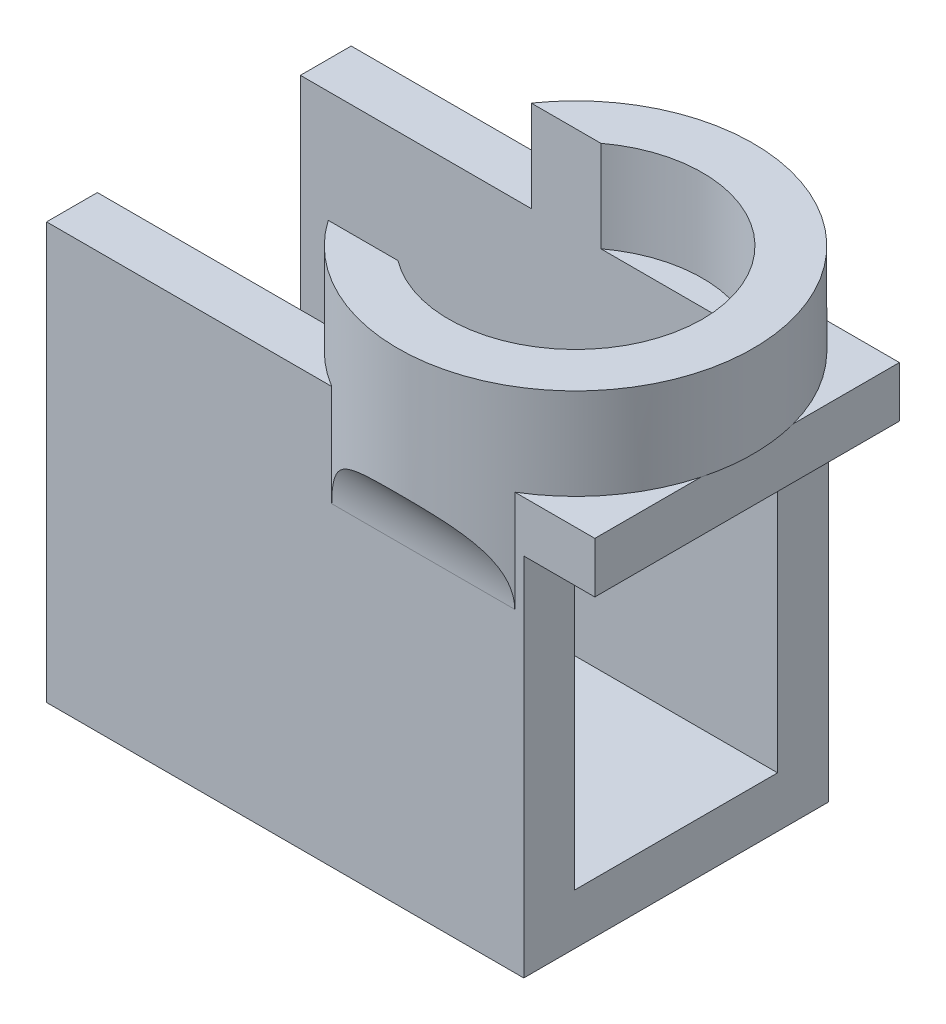
SolidWorks part; units mm, degrees
ref_plane "Front Plane" through (0, 0, 0) normal (0, 0, 1) x (1, 0, 0)
ref_plane "Top Plane" through (0, 0, 0) normal (0, 1, 0) x (1, 0, 0)
ref_plane "Right Plane" through (0, 0, 0) normal (1, 0, 0) x (0, 0, -1)
sketch "Sketch1" plane through (0, 0, 0) normal (0, 1, 0) x (1, 0, 0)
  line L1 (0, 0) -> (54, 0)
  line L2 (0, 0) -> (0, 30)
  line L3 (0, 30) -> (54, 30)
  line L4 (54, 0) -> (54, 30)
  dimension "D1" = 54
  dimension "D2" = 30
extrude "Boss-Extrude1" add sketch "Sketch1" along normal blind 5
sketch "Sketch2" plane through (0, 5, 0) normal (0, 1, 0) x (1, 0, 0)
  line L0 (54, 0) -> (54, 30) construction
  line L1 (0, 30) -> (54, 30)
  line L2 (0, 30) -> (0, 25)
  line L3 (0, 25) -> (54, 25)
  line L4 (54, 30) -> (54, 25)
  line L6 (0, 0) -> (54, 0)
  line L7 (0, 0) -> (0, 5)
  line L8 (0, 5) -> (54, 5)
  line L9 (54, 0) -> (54, 5)
  dimension "D1" = 5
  dimension "D2" = 5
extrude "Boss-Extrude2" add sketch "Sketch2" along normal blind 36
sketch "Sketch3" plane through (0, 41, 0) normal (0, 1, 0) x (1, 0, 0)
  line L5 (0, 25) -> (54, 25) construction
  line L6 (47, 25) -> (54, 25)
  line L7 (47, 25) -> (47, 5)
  line L8 (47, 5) -> (54, 5)
  line L9 (54, 25) -> (54, 5)
  dimension "D2" = 7
extrude "Boss-Extrude3" add sketch "Sketch3" against normal blind 10
sketch "Sketch6" plane through (0, 0, 0) normal (0, -1, 0) x (1, 0, 0)
  line L10 (54, -30) -> (0, -30) construction
  line L11 (54, 0) -> (47, 0)
  line L12 (54, 0) -> (54, -30)
  line L13 (54, -30) -> (47, -30)
  line L14 (47, 0) -> (47, -30)
  dimension "D2" = 7
extrude "Cut-Extrude2" cut sketch "Sketch6" against normal blind 36
sketch "Sketch7" plane through (0, 0, 0) normal (-1, 0, 0) x (0, 0, 1)
  line L0 (-30, 41) -> (-30, 0) construction
  line L1 (-30, 0) -> (0, 0) construction
  circle A0 centre (-27.5, 5) radius 1.5
  circle A1 centre (-2.5, 5) radius 1.5
  dimension "D1" = 3
  dimension "D2" = 2.5
  dimension "D3" = 5
  dimension "D4" = 2
extrude "Cut-Extrude3" cut sketch "Sketch7" against normal blind 5
sketch "Sketch8" plane through (0, 41, 0) normal (0, 1, 0) x (1, 0, 0)
  line L0 (54, 0) -> (54, 30) construction
  line L1 (22.7386, 25) -> (29.6, 25)
  line L3 (22.7386, 5) -> (29.6, 5)
  arc A0 (22.7386, 5) -> (22.7386, 25) centre (37.1, 15) ccw
  arc A1 (29.6, 5) -> (29.6, 25) centre (37.1, 15) ccw
  dimension "D1" = 25
  dimension "D2" = 35
  dimension "D3" = 16.9
extrude "Boss-Extrude4" add sketch "Sketch8" along normal blind 9
fillet "Fillet1" radius 10 2 edges at (37.1, 41, 0) (37.1, 41, -30)
